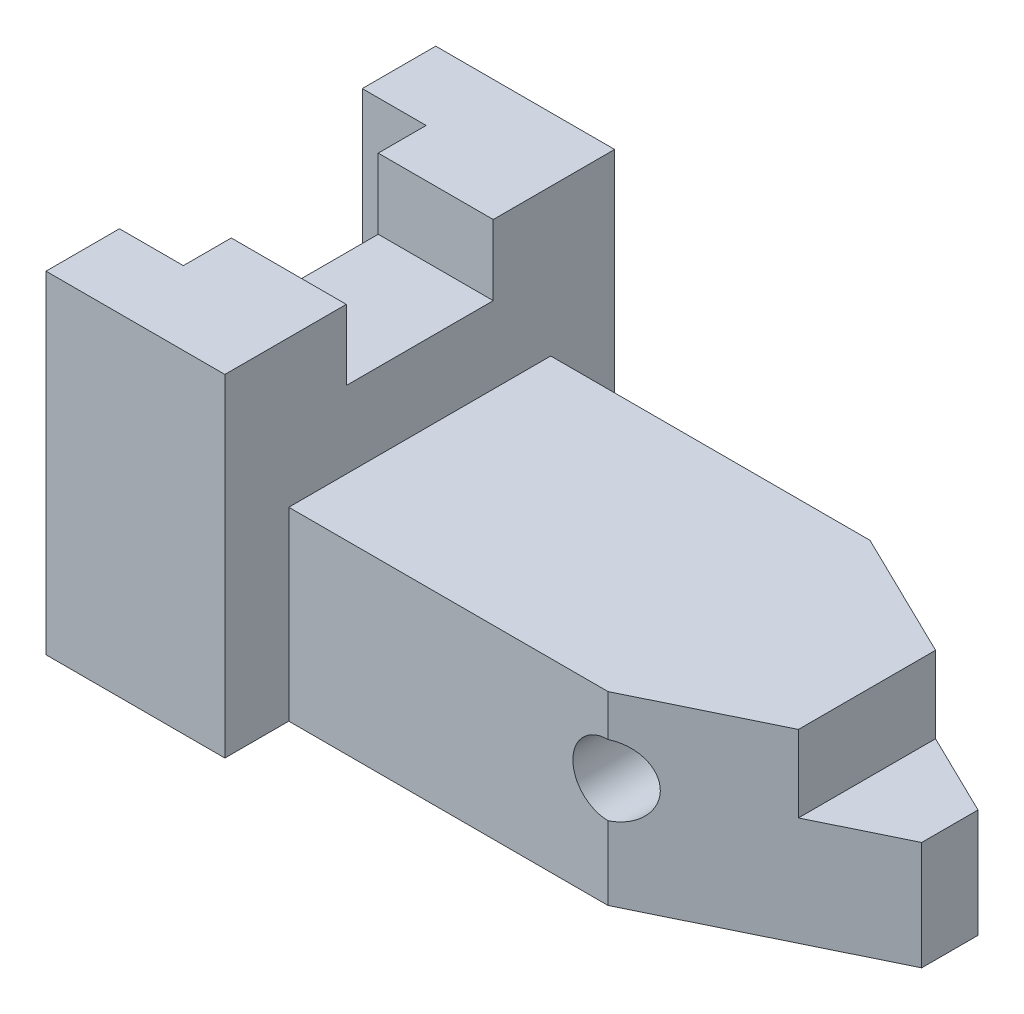
SolidWorks part; units mm, degrees
ref_plane "Front Plane" through (0, 0, 0) normal (0, 0, 1) x (1, 0, 0)
ref_plane "Top Plane" through (0, 0, 0) normal (0, 1, 0) x (1, 0, 0)
ref_plane "Right Plane" through (0, 0, 0) normal (1, 0, 0) x (0, 0, -1)
sketch "Sketch1" plane through (0, 0, 0) normal (0, 1, 0) x (1, 0, 0)
  line L0 (10, 19) -> (10, -19)
  line L1 (10, 19) -> (0, 19)
  line L2 (0, 19) -> (0, 30.5)
  line L3 (0, 30.5) -> (28, 30.5)
  line L4 (28, 30.5) -> (28, -30.5)
  line L5 (28, 20.5) -> (77.9688, 20.5)
  line L6 (77.9688, 20.5) -> (110.9688, 4.4048)
  line L7 (110.9688, 4.4048) -> (110.9688, -4.4048)
  line L8 (98, 10.7301) -> (98, -10.7301)
  line L9 (0, 0) -> (131.6735, 0) construction
  line L10 (110.9688, 4.4048) -> (120, 0) construction
  line L11 (110.9688, -4.4048) -> (120, 0) construction
  line L12 (77.9688, -20.5) -> (110.9688, -4.4048)
  line L13 (28, -20.5) -> (77.9688, -20.5)
  line L14 (0, -30.5) -> (28, -30.5)
  line L15 (0, -19) -> (0, -30.5)
  line L16 (10, -19) -> (0, -19)
  line L17 (10, 11.5) -> (28, 11.5)
  line L18 (10, -11.5) -> (28, -11.5)
  point P12 (110.9688, 0)
  point P17 (98, 0)
  point P21 (28, 0)
  point P24 (10, 0)
  dimension "D1" = 28
  dimension "D2" = 19
  dimension "D3" = 10
  dimension "D4" = 26
  dimension "D5" = 22
  dimension "D6" = 33
  dimension "D7" = 120
  dimension "D8" = 20.5
  dimension "D9" = 30.5
  dimension "D10" = 23
extrude "Boss-Extrude1" add sketch "Sketch1" along normal blind 52 contours L18 L0 L16 L15 L14 L4 | L0 L17 L4 L3 L2 L1 region at (15.477, 0, -21.9437) region at (15.477, 0, 21.9437)
extrude "Boss-Extrude2" add sketch "Sketch1<3>" along normal blind 41 contours L0 L18 L4 L17 region at (19, 0, 0)
sketch "Sketch1<3>" plane through (0, 0, 0) normal (0, 1, 0) x (1, 0, 0) same geometry as "Sketch1"
extrude "Boss-Extrude3" add sketch "Sketch1<4>" along normal blind 29 contours L4 L13 L12 L8 L6 L5 region at (60.9274, 0, 0)
sketch "Sketch1<4>" plane through (0, 0, 0) normal (0, 1, 0) x (1, 0, 0) same geometry as "Sketch1"
extrude "Boss-Extrude4" add sketch "Sketch1<5>" along normal blind 17 contours L8 L12 L7 L6 region at (103.5811, 0, 0)
sketch "Sketch1<5>" plane through (0, 0, 0) normal (0, 1, 0) x (1, 0, 0) same geometry as "Sketch1"
sketch "Sketch2" plane through (0, 0, 0) normal (0, 0, 1) x (1, 0, 0)
  line L0 (77.9688, 29) -> (77.9688, 0) construction
  line L1 (98, 17) -> (110.9688, 17) construction
  circle A0 centre (77.9688, 17) radius 5.5
  point P4 (0, 0)
  dimension "D1" = 11
extrude "Cut-Extrude1" cut sketch "Sketch2" against normal mid plane 61
